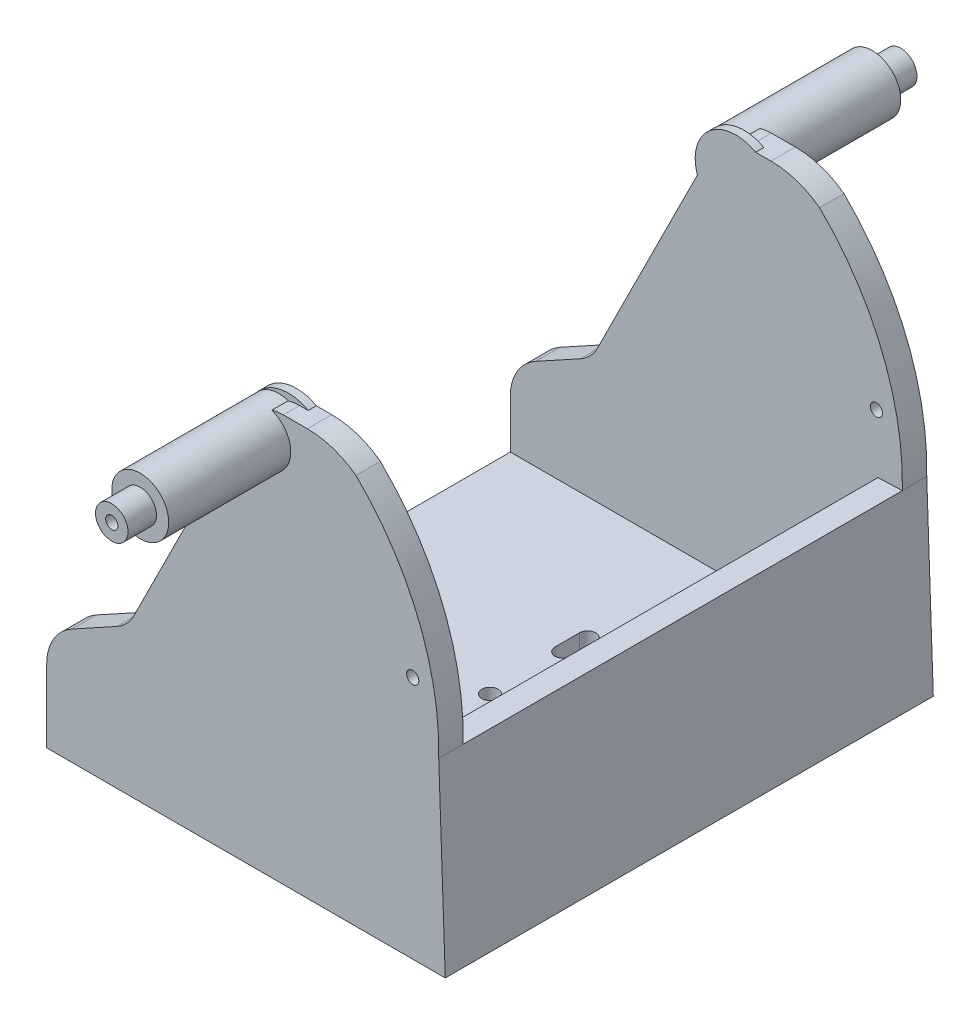
SolidWorks part; units mm, degrees
ref_plane "Plan de face" through (0, 0, 0) normal (0, 0, 1) x (1, 0, 0)
ref_plane "Plan de dessus" through (0, 0, 0) normal (0, 1, 0) x (1, 0, 0)
ref_plane "Plan de droite" through (0, 0, 0) normal (1, 0, 0) x (0, 0, -1)
sketch "Esquisse1" plane through (0, 0, 0) normal (0, 0, 1) x (1, 0, 0)
  line L0 (-45.8915, 14.2097) -> (-40.3656, 17.2489)
  line L1 (0, 0) -> (-49, 0)
  line L2 (0, 0) -> (-0.8032, 23)
  line L3 (-16.9518, 50) -> (-19.9098, 50)
  line L4 (-49, 0) -> (-49, 8.9524)
  line L5 (-38.303, 19.3939) -> (-24.382, 47.2361)
  arc A0 (-45.8915, 14.2097) -> (-49, 8.9524) centre (-43, 8.9524) ccw
  arc A1 (-38.303, 19.3939) -> (-40.3656, 17.2489) centre (-42.7752, 21.63) cw
  arc A2 (-19.9098, 50) -> (-24.382, 47.2361) centre (-19.9098, 45) ccw
  arc A3 (-0.8032, 23) -> (-10.977, 48.0189) centre (-34.7948, 23.7554) ccw
  arc A4 (-10.977, 48.0189) -> (-16.9518, 50) centre (-16.9518, 40) ccw
  circle A5 centre (-4, 30) radius 0.75
  point P12 (-39, 18)
  point P16 (-0.8032, 23)
  dimension "D3" = 6
  dimension "D7" = 5
  dimension "D6" = 5
  dimension "D2" = 20
  dimension "D9" = 34
  dimension "D12" = 30
  dimension "D13" = 4
  dimension "D14" = 1.5
  dimension "D1" = 49
  dimension "D4" = 18
  dimension "D5" = 10
  dimension "D8" = 23
  dimension "D10" = 50
  dimension "D11" = 88
extrude "Boss.-Extru.1" add sketch "Esquisse1" along normal blind 60
sketch "Esquisse3" plane through (0, 0, 0) normal (0, 0, -1) x (-1, 0, 0)
  line L0 (49, 0) -> (0, 0) construction
  line L1 (49, 8.9524) -> (49, 0) construction
  circle A0 centre (22.5, 46.5) radius 3.5
  dimension "D1" = 7
  dimension "D2" = 46.5
  dimension "D3" = 26.5
extrude "Boss.-Extru.2" add sketch "Esquisse3" along normal blind 15 and the other way blind 75
sketch "Esquisse9" plane through (0, 0, 75) normal (0, 0, 1) x (1, 0, 0)
  circle A0 centre (-22.5, 46.5) radius 2
  dimension "D1" = 4
extrude "Boss.-Extru.6" add sketch "Esquisse9" along normal blind 3.5 and the other way blind 93.5
sketch "Esquisse2" plane through (0, 0, 0) normal (0.9994, 0.0349, 0) x (0, 0, -1)
  line L0 (0, 23.014) -> (0, 48.3727) construction
  line L1 (-57, 23) -> (-3, 23)
  line L2 (-57, 23) -> (-57, 72.8933)
  line L3 (-57, 72.8933) -> (-3, 72.8933)
  line L4 (-3, 23) -> (-3, 72.8933)
  line L5 (-60, 0) -> (0, 0) construction
  dimension "D1" = 54
  dimension "D2" = 3
  dimension "D3" = 23
extrude "Enlèv. mat.-Extru.1" cut sketch "Esquisse2" against normal blind 60 and the other way blind 60
shell "Coque1" thickness 3 removed face at (-49, 4.4762, 30) removed face at (-47.8052, 11.7936, 30) removed face at (-31.6514, 32.6971, 30) removed face at (-39.2527, 18.2429, 30) removed face at (-43.1285, 15.7293, 30) removed face at (-18.9721, 22.3515, 30)
sketch "Esquisse4" plane through (0, 0, 3) normal (0, 0, 1) x (1, 0, 0)
  circle A0 centre (-21.2767, 45.6319) radius 5
  arc A1 (-21.323, 49.7961) -> (-25.5806, 44.8388) centre (-22.5, 46.5) ccw construction
  dimension "D1" = 10
extrude "Boss.-Extru.3" add sketch "Esquisse4" against normal blind 1
sketch "Esquisse5" plane through (0, 0, 57) normal (0, 0, -1) x (-1, 0, 0)
  circle A2 centre (21.2767, 45.6319) radius 5
extrude "Boss.-Extru.4" add sketch "Esquisse5" against normal blind 1
sketch "Esquisse6" plane through (0, 0, 0) normal (0, -1, 0) x (1, 0, 0)
  line L0 (-12.5, 30) -> (-15.5, 30) construction
  line L1 (-12.5, 29) -> (-15.5, 29)
  line L2 (-12.5, 31) -> (-15.5, 31)
  line L3 (0, 60) -> (0, 0) construction
  line L4 (-49, 60) -> (0, 60) construction
  line L5 (-24.5, 18) -> (-24.5, 21) construction
  line L6 (-25.5, 18) -> (-25.5, 21)
  line L7 (-23.5, 18) -> (-23.5, 21)
  line L8 (-36.5, 30) -> (-33.5, 30) construction
  line L9 (-36.5, 31) -> (-33.5, 31)
  line L10 (-36.5, 29) -> (-33.5, 29)
  line L11 (-24.5, 42) -> (-24.5, 39) construction
  line L12 (-23.5, 42) -> (-23.5, 39)
  line L13 (-25.5, 42) -> (-25.5, 39)
  circle A0 centre (-24.5, 30) radius 1
  arc A1 (-12.5, 29) -> (-12.5, 31) centre (-12.5, 30) ccw
  arc A2 (-15.5, 31) -> (-15.5, 29) centre (-15.5, 30) ccw
  arc A3 (-25.5, 18) -> (-23.5, 18) centre (-24.5, 18) ccw
  arc A4 (-23.5, 21) -> (-25.5, 21) centre (-24.5, 21) ccw
  arc A5 (-36.5, 31) -> (-36.5, 29) centre (-36.5, 30) ccw
  arc A6 (-33.5, 29) -> (-33.5, 31) centre (-33.5, 30) ccw
  arc A7 (-23.5, 42) -> (-25.5, 42) centre (-24.5, 42) ccw
  arc A8 (-25.5, 39) -> (-23.5, 39) centre (-24.5, 39) ccw
  circle A9 centre (-15, 40) radius 1.75
  point P4 (-14, 30)
  point P9 (0, 30)
  point P18 (-24.5, 19.5)
  point P25 (-35, 30)
  point P32 (-24.5, 40.5)
  dimension "D1" = 2
  dimension "D2" = 24.5
  dimension "D3" = 30
  dimension "D4" = 1
  dimension "D6" = 9
  dimension "D8" = 3.5
  dimension "D9" = 15
  dimension "D10" = 20
  dimension "D5" = 3
  dimension "D7" = 4
extrude "Enlèv. mat.-Extru.2" cut sketch "Esquisse6" against normal through all
sketch "Esquisse7" plane through (0, 0, 0) normal (0, -1, 0) x (1, 0, 0)
  circle A0 centre (-24.5, 30) radius 4.25
  dimension "D1" = 8.5
extrude "Boss.-Extru.5" add sketch "Esquisse7" along normal blind 3
sketch "Esquisse8" plane through (0, -3, 0) normal (0, -1, 0) x (1, 0, 0)
  circle A0 centre (-24.5, 30) radius 3
  circle A1 centre (-24.5, 30) radius 4.25 construction
  dimension "D1" = 6
extrude "Enlèv. mat.-Extru.3" cut sketch "Esquisse8" against normal blind 3.5
sketch "Esquisse10" plane through (0, 0, 78.5) normal (0, 0, 1) x (1, 0, 0)
  circle A0 centre (-22.5, 46.5) radius 0.75
  dimension "D1" = 1.5
extrude "Enlèv. mat.-Extru.4" cut sketch "Esquisse10" against normal blind 5
sketch "Esquisse11" plane through (0, 0, -18.5) normal (0, 0, -1) x (-1, 0, 0)
  circle A0 centre (22.5, 46.5) radius 0.75
  dimension "D1" = 1.5
extrude "Enlèv. mat.-Extru.5" cut sketch "Esquisse11" against normal blind 5
